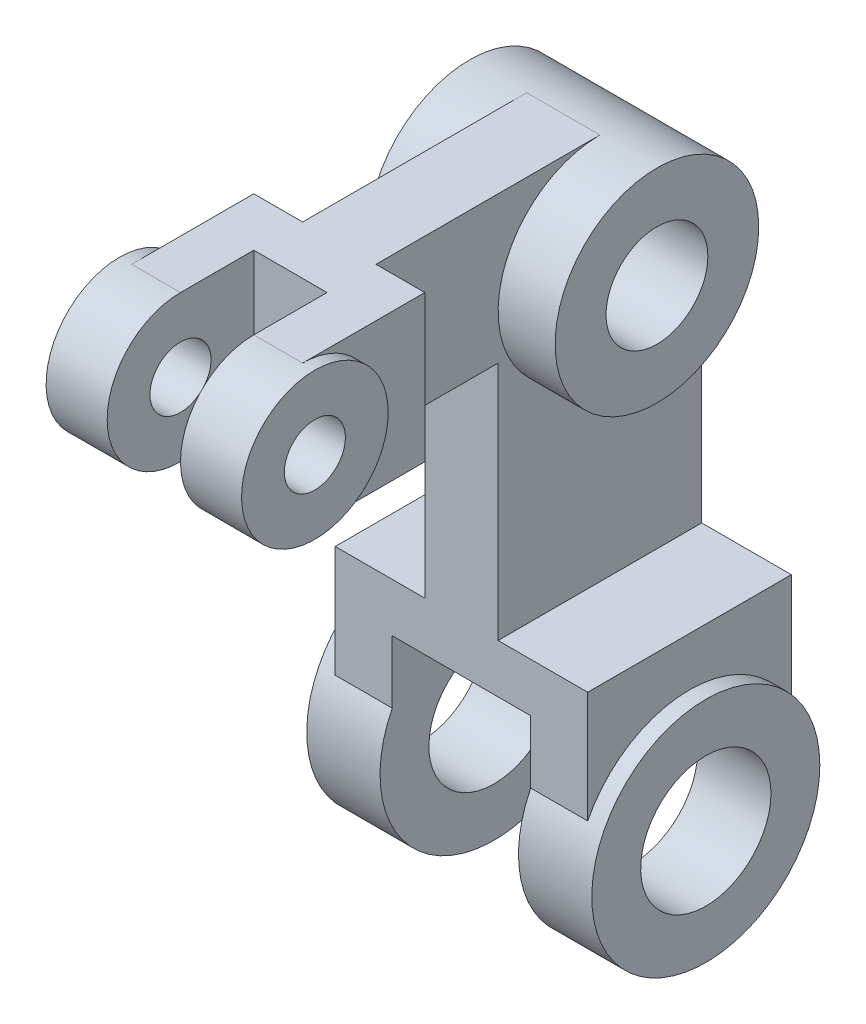
SolidWorks part; units mm, degrees
other "Markup1"
sketch "Sketch4" plane through (35, 135, 103) normal (0.5774, 0.5773, 0.5774) x (0.7071, 0, -0.7071)
material "Titanium"
ref_plane "Front Plane" through (0, 0, 0) normal (0, 0, 1) x (1, 0, 0)
ref_plane "Top Plane" through (0, 0, 0) normal (0, 1, 0) x (1, 0, 0)
ref_plane "Right Plane" through (0, 0, 0) normal (1, 0, 0) x (0, 0, -1)
sketch "Sketch1" plane through (0, 0, 0) normal (1, 0, 0) x (0, 0, -1)
  line L0 (-25, 110) -> (-25, 12.6095)
  line L1 (25, 110) -> (25, 12.6095)
  line L2 (0, 110) -> (0, 0) construction
  line L3 (-25, 40) -> (25, 40)
  line L4 (-85, 135) -> (0, 135)
  line L5 (-85, 99) -> (-25, 99)
  line L6 (-55, 135) -> (-55, 99)
  circle A0 centre (0, 0) radius 28
  circle A1 centre (0, 0) radius 16
  circle A2 centre (0, 110) radius 25
  circle A3 centre (0, 110) radius 12.5
  circle A4 centre (-85, 117) radius 7.5
  circle A5 centre (-85, 117) radius 18
  point P22 (-79.2174, 117)
  dimension "D1" = 56
  dimension "D2" = 32
  dimension "D3" = 50
  dimension "D4" = 25
  dimension "D7" = 36
  dimension "D8" = 15
  dimension "D5" = 110
  dimension "D6" = 70
  dimension "D9" = 55
  dimension "D10" = 30
extrude "Boss-Extrude1" add sketch "Sketch1" along normal mid plane 18 contours A2 L2 L3 L1 | L2 A2 L0 L3 | A2 L4 L6 L5 L0 region at (0, 65.4916, 13.2367) region at (0, 118.3716, 37.726) region at (0, 65.4916, -13.2367)
extrude "Boss-Extrude2" add sketch "Sketch1<3>" along normal mid plane 46 contours A3 A2 region at (0, 127.1777, 17.1777)
sketch "Sketch1<3>" plane through (0, 0, 0) normal (1, 0, 0) x (0, 0, -1) same geometry as "Sketch1"
extrude "Boss-Extrude3" add sketch "Sketch1<5>" along normal mid plane 70 separate body contours A0 A1 region at (0, 27.208, 0)
sketch "Sketch1<5>" plane through (0, 0, 0) normal (1, 0, 0) x (0, 0, -1) same geometry as "Sketch1"
extrude "Boss-Extrude4" add sketch "Sketch1<6>" along normal mid plane 62 contours L3 L2 A0 L1 | L2 L3 L0 A0 region at (0, 31.2487, 14.2794) region at (0, 31.2487, -14.2794)
sketch "Sketch1<6>" plane through (0, 0, 0) normal (1, 0, 0) x (0, 0, -1) same geometry as "Sketch1"
extrude "Boss-Extrude5" add sketch "Sketch1<7>" along normal mid plane 42 contours A5 L5 L6 L4 region at (0, 117, 63.4402)
sketch "Sketch1<7>" plane through (0, 0, 0) normal (1, 0, 0) x (0, 0, -1) same geometry as "Sketch1"
extrude "Boss-Extrude6" add sketch "Sketch1<8>" along normal mid plane 48 contours A5 A4 region at (0, 117, 102.4909)
sketch "Sketch1<8>" plane through (0, 0, 0) normal (1, 0, 0) x (0, 0, -1) same geometry as "Sketch1"
sketch "Sketch2" plane through (0, 0, 0) normal (0, 0, 1) x (1, 0, 0)
  line L0 (-35, -28) -> (35, -28) construction
  line L1 (-17, 28) -> (17, 28)
  line L2 (-17, 28) -> (-17, -28)
  line L3 (-17, -28) -> (17, -28)
  line L4 (17, 28) -> (17, -28)
  line L5 (-9, 40) -> (-31, 40) construction
  point P4 (0, -28)
  point P6 (13.3869, -28)
  dimension "D1" = 34
  dimension "D2" = 12
extrude "Cut-Extrude1" cut sketch "Sketch2" against normal through all both and the other way through all
sketch "Sketch3" plane through (0, 135, 0) normal (0, 1, 0) x (1, 0, 0)
  line L0 (-9, -55) -> (-21, -55) construction
  line L1 (-9, -67) -> (9, -67)
  line L2 (-9, -67) -> (-9, -103)
  line L3 (-9, -103) -> (9, -103)
  line L4 (9, -67) -> (9, -103)
  line L5 (9, -55) -> (9, 0) construction
  line L6 (-9, -55) -> (-9, 0) construction
  dimension "D1" = 12
extrude "Cut-Extrude2" cut sketch "Sketch3" against normal through all both
equation "\"D1@Boss-Extrude3\"=18+34+18"
equation "\"D1@Boss-Extrude4\"=22+18+22"
equation "\"D1@Boss-Extrude5\"=12+18+12"
equation "\"D1@Boss-Extrude6\"=15+18+15"
